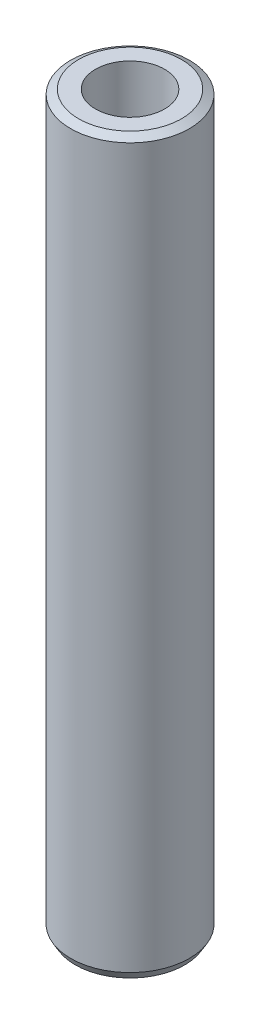
SolidWorks part; units mm, degrees
ref_plane "Front Plane" through (0, 0, 0) normal (0, 0, 1) x (1, 0, 0)
ref_plane "Top Plane" through (0, 0, 0) normal (0, 1, 0) x (1, 0, 0)
ref_plane "Right Plane" through (0, 0, 0) normal (1, 0, 0) x (0, 0, -1)
sketch "Sketch1" plane through (0, 0, 0) normal (0, 1, 0) x (1, 0, 0)
  circle A0 centre (0, 0) radius 7.5
  dimension "SHAFT_OD" = 15
extrude "Boss-Extrude1" add sketch "Sketch1" along normal blind 92.361
sketch "Sketch2" plane through (0, 0, 0) normal (0, 1, 0) x (1, 0, 0)
  circle A0 centre (0, 0) radius 4.3614
  dimension "BORE_D" = 8.7228
extrude "Cut-Extrude1" cut sketch "Sketch2" along normal through all
chamfer "Chamfer1" distance 0.5788 angle 60 2 edges at (0, 92.361, 7.5) (0, 0, 7.5) first distance on face at (0, 92.361, 7.5) first distance on face at (0, 0, 4.3614)
